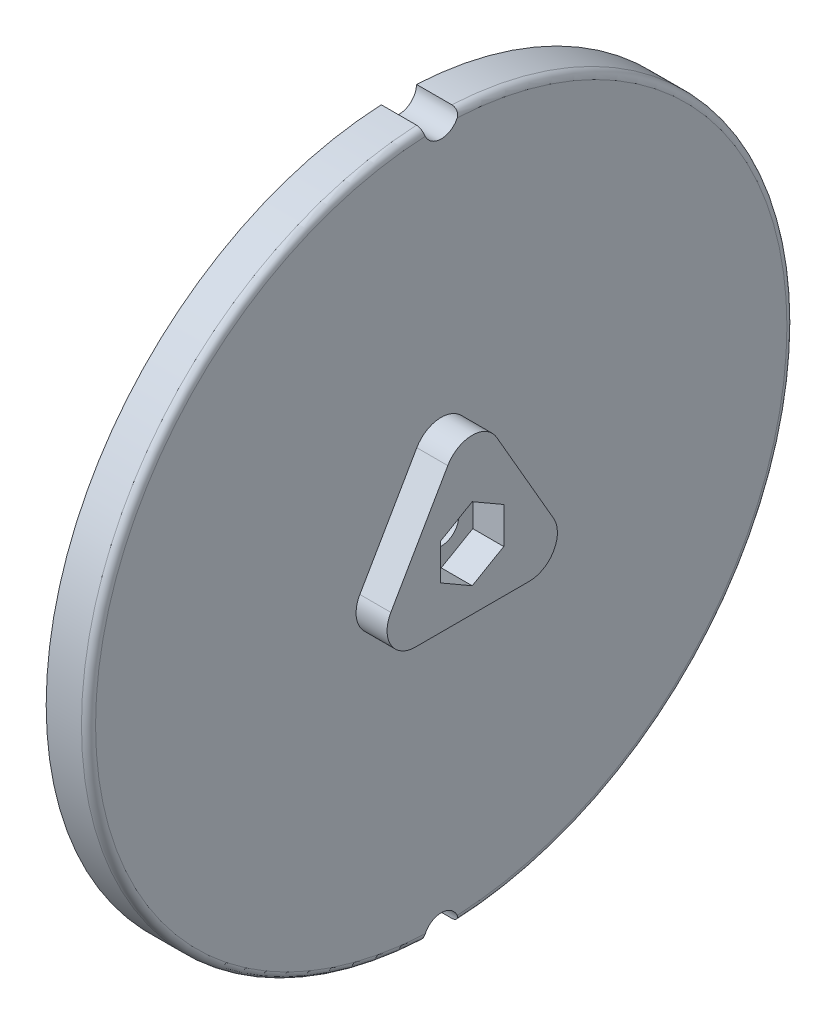
SolidWorks part; units mm, degrees
ref_plane "Front Plane" through (0, 0, 0) normal (0, 0, 1) x (1, 0, 0)
ref_plane "Top Plane" through (0, 0, 0) normal (0, 1, 0) x (1, 0, 0)
ref_plane "Right Plane" through (0, 0, 0) normal (1, 0, 0) x (0, 0, -1)
sketch "Sketch2" plane through (0, 0, 0) normal (1, 0, 0) x (0, 0, -1)
  line L0 (55, 0) -> (-55, 0) construction
  arc A0 (3.1742, -63.4206) -> (3.1742, 63.4206) centre (0, 0) ccw
  circle A1 centre (0, 0) radius 3.175
  arc A2 (-3.1738, -63.4206) -> (3.1742, -63.4206) centre (0.0002, -63.5) cw
  arc A3 (-3.1738, 63.4206) -> (3.1742, 63.4206) centre (0.0002, 63.5) ccw
  arc A4 (-3.1738, 63.4206) -> (-3.1738, -63.4206) centre (0, 0) ccw
  dimension "D1" = 127
  dimension "D2" = 6.35
extrude "Boss-Extrude1" add sketch "Sketch2" along normal blind 7.62
sketch "Sketch3" plane through (7.62, 0, 0) normal (1, 0, 0) x (0, 0, -1)
  line L0 (-5.675, 3.2765) -> (-5.675, -3.2765)
  line L1 (19.05, -10.9985) -> (0, 21.997)
  line L2 (0, 21.997) -> (-19.05, -10.9985)
  line L3 (-19.05, -10.9985) -> (19.05, -10.9985)
  line L4 (5.675, -3.2765) -> (5.675, 3.2765)
  line L5 (5.675, 3.2765) -> (0, 6.5529)
  line L6 (0, 6.5529) -> (-5.675, 3.2765)
  line L7 (-5.675, -3.2765) -> (0, -6.5529)
  line L8 (0, -6.5529) -> (5.675, -3.2765)
  circle A0 centre (0, 0) radius 10.9985 construction
  circle A1 centre (0, 0) radius 5.675 construction
  dimension "D1" = 11.35
  dimension "D2" = 38.1
extrude "Boss-Extrude2" add sketch "Sketch3" along normal blind 5.58
fillet "Fillet1" radius 5.08 3 edges at (10.41, -10.9985, -19.05) (10.41, 21.997, 0) (10.41, -10.9985, 19.05)
fillet "Fillet3" radius 1.27 2 edges at (7.62, 0, -63.5) (7.62, 0, 63.5)
